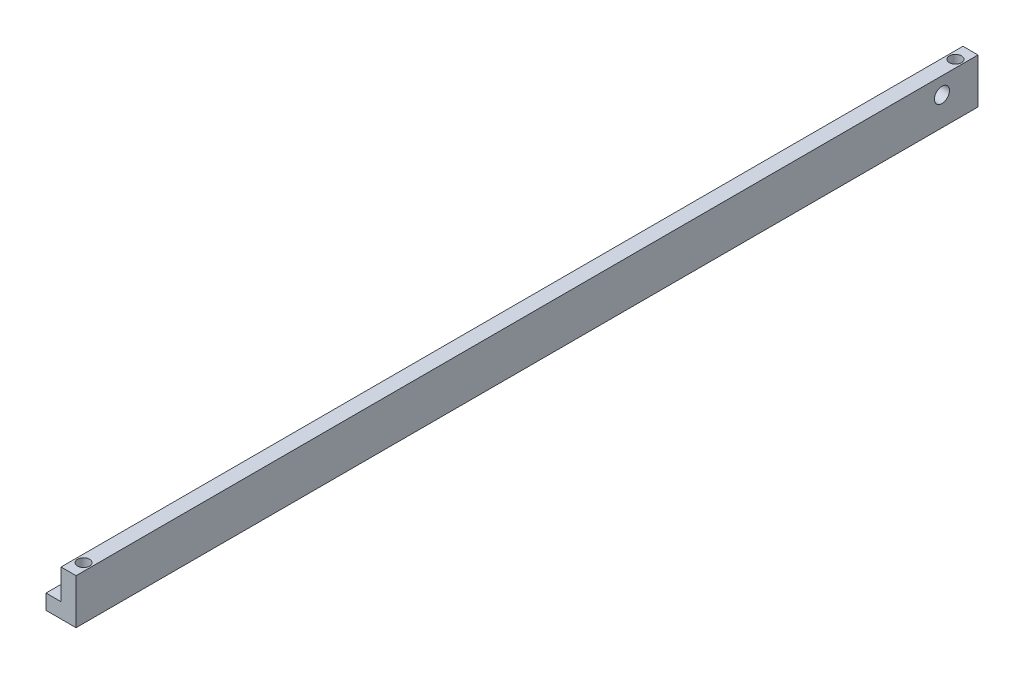
SolidWorks part; units mm, degrees
ref_plane "Front Plane" through (0, 0, 0) normal (0, 0, 1) x (1, 0, 0)
ref_plane "Top Plane" through (0, 0, 0) normal (0, 1, 0) x (1, 0, 0)
ref_plane "Right Plane" through (0, 0, 0) normal (1, 0, 0) x (0, 0, -1)
sketch "Sketch1" plane through (0, 0, 0) normal (0, 0, 1) x (1, 0, 0)
  line L0 (0, 0) -> (-6.35, 0)
  line L3 (-6.35, 0) -> (-6.35, 19.05)
  line L4 (-6.35, 19.05) -> (0, 19.05)
  line L5 (0, 19.05) -> (0, 0)
  point P1 (0, 0)
  point P5 (-6.35, 0)
  dimension "D1" = 19.05
  dimension "D4" = 6.35
extrude "Boss-Extrude1" add sketch "Sketch1" along normal blind 381 contours L3 L0 L5 L4 region at (-3.175, 9.525, 0)
sketch "Sketch2" plane through (0, 19.05, 0) normal (0, 1, 0) x (1, 0, 0)
  line L0 (-3.175, 0) -> (-3.175, -381) construction
  line L3 (-6.35, 0) -> (0, 0) construction
  line L4 (-6.35, -381) -> (0, -381) construction
  circle A0 centre (-3.175, -374.65) radius 2.54
  circle A1 centre (-3.175, -6.35) radius 2.54
  point P2 (0, 0)
  point P4 (0, 0)
  point P5 (-3.175, -381.1552)
  point P14 (0, 0)
  point P15 (0, 0)
  point P16 (0, 0)
  dimension "D1" = 5.08
  dimension "D2" = 6.35
  dimension "D3" = 6.35
sketch "Sketch3" plane through (0, 0, 0) normal (0, -1, 0) x (1, 0, 0)
  line L0 (-3.175, 0) -> (-3.175, 381) construction
  line L3 (0, 381) -> (0, 0) construction
  line L4 (0, 0) -> (-6.35, 0) construction
  line L5 (0, 381) -> (-6.35, 381) construction
  circle A0 centre (-3.175, 374.65) radius 2.54
  circle A1 centre (-3.175, 6.35) radius 2.54
  point P2 (0, 0)
  point P4 (0, 0)
  point P5 (-3.175, 384.3498)
  point P16 (0, 0)
  point P17 (0, 0)
  dimension "D2" = 5.08
  dimension "D1" = 3.175
  dimension "D3" = 6.35
  dimension "D4" = 6.35
sketch "Sketch4" plane through (0, 0, 0) normal (1, 0, 0) x (0, 0, -1)
  line L1 (-381, 19.05) -> (-381, 0) construction
  line L3 (-381, 19.05) -> (0, 19.05) construction
  circle A0 centre (-15.24, 12.065) radius 3.175
  dimension "D3" = 6.35
  dimension "D1" = 365.76
  dimension "D2" = 6.985
extrude "Boss-Extrude2" add sketch "Sketch1<3>" along normal blind 25.4 contours L0 region at (-3.175, 9.525, 0)
sketch "Sketch1<3>" plane through (0, 0, 0) normal (0, 0, 1) x (1, 0, 0) same geometry as "Sketch1"
extrude "Cut-Extrude3" cut sketch "Sketch4" against normal blind 25.4
sketch "Sketch5" plane through (0, 0, 381) normal (0, 0, 1) x (1, 0, 0)
  line L1 (-6.35, 0) -> (-12.7, 0)
  line L2 (-6.35, 0) -> (-6.35, 6.35)
  line L3 (-6.35, 6.35) -> (-12.7, 6.35)
  line L4 (-12.7, 0) -> (-12.7, 6.35)
  dimension "D1" = 6.35
  dimension "D2" = 6.35
extrude "Boss-Extrude3" add sketch "Sketch5" against normal blind 35.56
extrude "Cut-Extrude4" cut sketch "Sketch2" against normal blind 7.62
extrude "Cut-Extrude5" cut sketch "Sketch3" against normal blind 7.62
